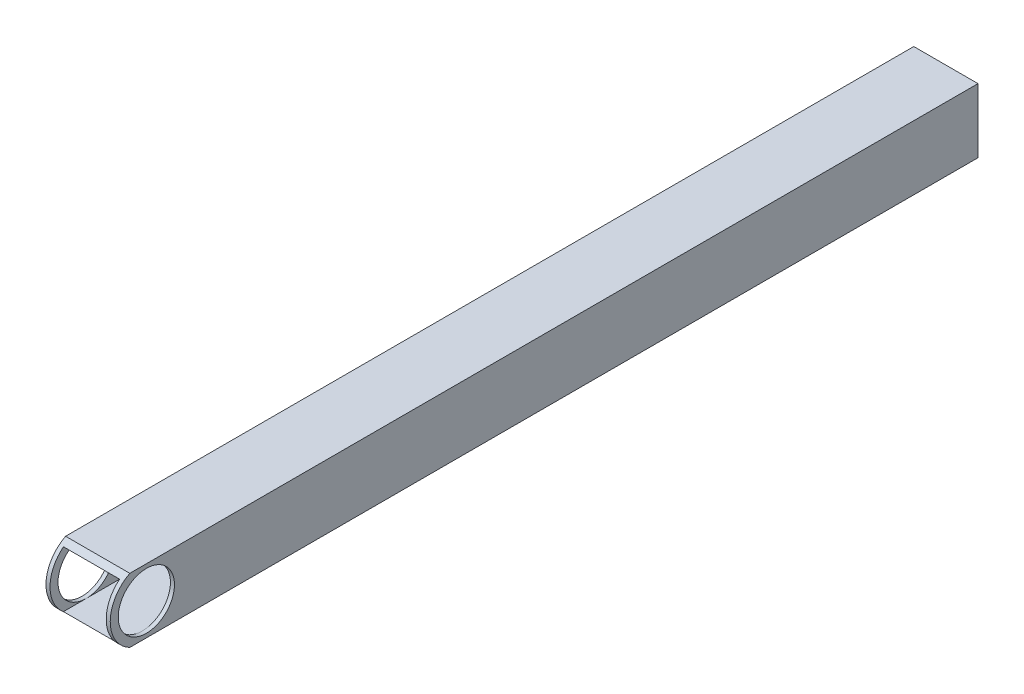
SolidWorks part; units mm, degrees
material "6061 Alloy"
ref_plane "Front Plane" through (0, 0, 0) normal (0, 0, 1) x (1, 0, 0)
ref_plane "Top Plane" through (0, 0, 0) normal (0, 1, 0) x (1, 0, 0)
ref_plane "Right Plane" through (0, 0, 0) normal (1, 0, 0) x (0, 0, -1)
sketch "Sketch1" plane through (0, 0, 0) normal (0, 0, 1) x (1, 0, 0)
  line L1 (12.7, -12.7) -> (-12.7, -12.7)
  line L2 (12.7, -12.7) -> (12.7, 12.7)
  line L3 (12.7, 12.7) -> (-12.7, 12.7)
  line L4 (-12.7, -12.7) -> (-12.7, 12.7)
  line L5 (12.7, -12.7) -> (-12.7, 12.7) construction
  line L6 (12.7, 12.7) -> (-12.7, -12.7) construction
  point P0 (0, 0)
  dimension "D1" = 25.4
extrude "Extrude-Thin1" add sketch "Sketch1" along normal mid plane 347.98 thin thin type one direction reverse wall 1.5875
sketch "Sketch2" plane through (12.7, 0, 0) normal (1, 0, 0) x (0, 0, -1)
  line L0 (-173.99, -12.7) -> (-173.99, 12.7) construction
  line L1 (-173.99, -12.7) -> (173.99, -12.7) construction
  circle A0 centre (-154.94, 0) radius 11.1125
  dimension "D1" = 22.225
  dimension "D2" = 19.05
  dimension "D3" = 12.7
extrude "Cut-Extrude1" cut sketch "Sketch2" against normal through all
sketch "Sketch3" plane through (12.7, 0, 0) normal (1, 0, 0) x (0, 0, -1)
  line L0 (-154.94, 14.2875) -> (-173.99, 14.2875)
  line L3 (-173.99, 14.2875) -> (-173.99, -12.7)
  line L4 (-173.99, -12.7) -> (-161.4854, -12.7)
  arc A0 (-154.94, 14.2875) -> (-161.4854, -12.7) centre (-154.94, 0) ccw
  circle A1 centre (-154.94, 0) radius 11.1125 construction
  dimension "D1" = 3.175
extrude "Cut-Extrude2" cut sketch "Sketch3" against normal through all
